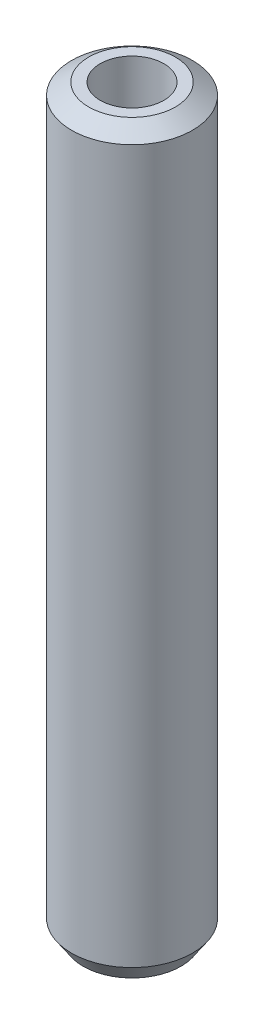
SolidWorks part; units mm, degrees
ref_plane "Front Plane" through (0, 0, 0) normal (0, 0, 1) x (1, 0, 0)
ref_plane "Top Plane" through (0, 0, 0) normal (0, 1, 0) x (1, 0, 0)
ref_plane "Right Plane" through (0, 0, 0) normal (1, 0, 0) x (0, 0, -1)
sketch "Sketch1" plane through (0, 0, 0) normal (0, 1, 0) x (1, 0, 0)
  circle A0 centre (0, 0) radius 20
  dimension "SHAFT_OD" = 40
extrude "Boss-Extrude1" add sketch "Sketch1" along normal blind 245.0641
sketch "Sketch2" plane through (0, 0, 0) normal (0, 1, 0) x (1, 0, 0)
  circle A0 centre (0, 0) radius 10.5239
  dimension "BORE_D" = 21.0479
extrude "Cut-Extrude1" cut sketch "Sketch2" along normal through all
chamfer "Chamfer1" distance 3.8155 angle 56.126 2 edges at (0, 245.0641, 20) (0, 0, 20) first distance on face at (0, 245.0641, 20) first distance on face at (0, 0, 10.5239)
